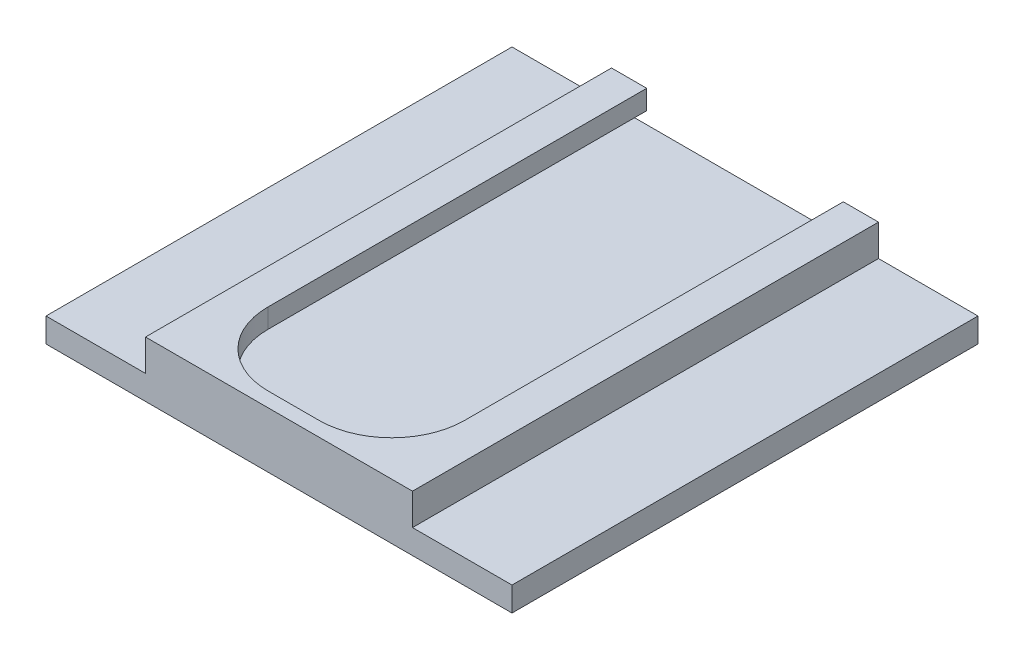
SolidWorks part; units mm, degrees
ref_plane "Front Plane" through (0, 0, 0) normal (0, 0, 1) x (1, 0, 0)
ref_plane "Top Plane" through (0, 0, 0) normal (0, 1, 0) x (1, 0, 0)
ref_plane "Right Plane" through (0, 0, 0) normal (1, 0, 0) x (0, 0, -1)
sketch "Sketch1" plane through (0, 0, 0) normal (0, 1, 0) x (1, 0, 0)
  line L0 (-48, 48) -> (-48, -48)
  line L1 (-45, 45) -> (45, 45)
  line L2 (-45, 45) -> (-45, -45)
  line L3 (-45, -45) -> (45, -45)
  line L4 (45, 45) -> (45, -45)
  line L5 (-45, 45) -> (45, -45) construction
  line L6 (-45, -45) -> (45, 45) construction
  line L7 (-48, -48) -> (48, -48)
  line L8 (48, 48) -> (48, -48)
  line L9 (-48, 48) -> (48, 48)
  point P0 (0, 0)
  dimension "D1" = 90
  dimension "D2" = 3
extrude "Boss-Extrude1" add sketch "Sketch1" along normal blind 2 contours L4 L1 L2 L3 | L9 L0 L7 L8 L1 L4 L3 L2 | L2 L1 L4 L3 | L0 L7 L8 L9 region at (0, 0, -46.6424) region at (0, 0, 0)
extrude "Boss-Extrude2" add sketch "Sketch1<3>" against normal blind 3 contours L9 L0 L7 L8 L1 L4 L3 L2 region at (0, 0, -46.6424)
sketch "Sketch1<3>" plane through (0, 0, 0) normal (0, 1, 0) x (1, 0, 0) same geometry as "Sketch1"
sketch "Sketch3" plane through (0, 0, 48) normal (0, 0, 1) x (1, 0, 0)
  line L0 (-48, 2) -> (48, 2) construction
  line L1 (-27.5, 2) -> (27.5, 2)
  line L2 (-27.5, 2) -> (-27.5, 8.5)
  line L3 (-27.5, 8.5) -> (27.5, 8.5)
  line L4 (27.5, 2) -> (27.5, 8.5)
  line L6 (-24.25, 4.5) -> (24.25, 4.5)
  line L7 (-24.25, 4.5) -> (-24.25, 2)
  line L8 (-24.25, 2) -> (24.25, 2)
  line L9 (24.25, 4.5) -> (24.25, 2)
  line L10 (20.25, 8.5) -> (-20.25, 8.5)
  line L11 (20.25, 8.5) -> (20.25, 4.5)
  line L12 (20.25, 4.5) -> (-20.25, 4.5)
  line L13 (-20.25, 8.5) -> (-20.25, 4.5)
  point P6 (0, 2)
  point P7 (0, 2)
  point P12 (0, 2)
  point P13 (0, 4.5)
  point P18 (0, 4.5)
  line M11 (48, 2) -> (-48, 2)
  dimension "D1" = 2.5
  dimension "D2" = 4
  dimension "D3" = 55
  dimension "D4" = 48.5
  dimension "D5" = 40.5
extrude "Boss-Extrude3" add sketch "Sketch3" against normal up to surface (96 mm away) contours L13 L3 L2 L1 L7 L6 | L3 L11 L6 L9 L4 M11 region at (-24.3127, 5.7887, 48) region at (24.3127, 5.7887, 48) up to face at (0, -0.5, -48)
extrude "Boss-Extrude4" add sketch "Sketch3<3>" against normal blind 3 contours L9 L6 L7 L1 | L3 L13 L6 L11 region at (0, 3.25, 48) region at (0, 6.5, 48)
sketch "Sketch3<3>" plane through (0, 0, 48) normal (0, 0, 1) x (1, 0, 0) same geometry as "Sketch3"
fillet "Fillet1" radius 15 2 edges at (20.25, 6.5, 45) (-20.25, 6.5, 45)
